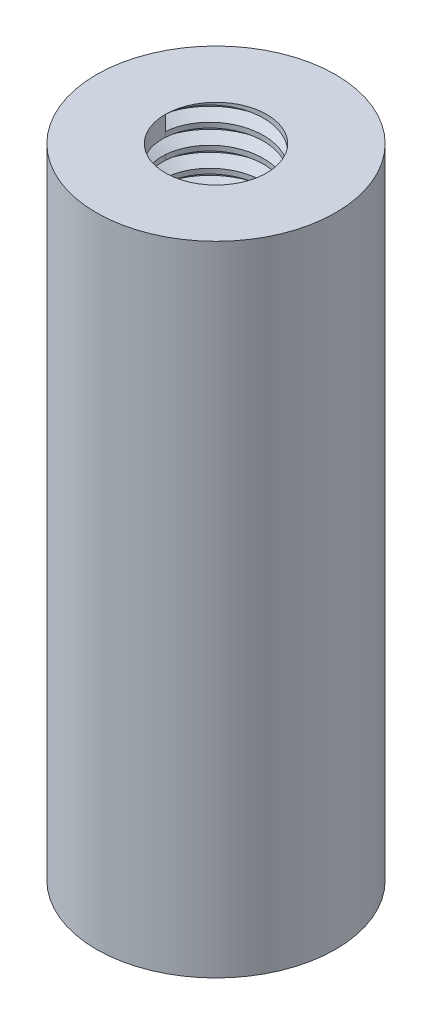
SolidWorks part; units mm, degrees
material "6061-T6 (SS)"
ref_plane "Front Plane" through (0, 0, 0) normal (0, 0, 1) x (1, 0, 0)
ref_plane "Top Plane" through (0, 0, 0) normal (0, 1, 0) x (1, 0, 0)
ref_plane "Right Plane" through (0, 0, 0) normal (1, 0, 0) x (0, 0, -1)
other "Bounding Box"
ref_plane "Default Plane" through (13.8565, 3.175, 6.7999) normal (0, -1, 0) x (-1, 0, 0)
sketch "Sketch1" plane through (0, 0, 0) normal (0, 1, 0) x (1, 0, 0)
  circle A0 centre (0, 0) radius 4.7625
  circle A1 centre (0, 0) radius 2.0193
  dimension "D1" = 9.525
  dimension "D2" = 4.0386
extrude "Boss-Extrude1" add sketch "Sketch1" along normal mid plane 25.4
thread "Thread1" pitch 0.7937 method cut profile "Thread Profile2" start angle 0, offset 0, length 9.525, pitch 0.7937, diameter 4.0386
ref_plane "Plane2" through (-2.0193, 12.7, 0) normal (0, 0, 1) x (-1, 0, 0)
sketch "Thread Profile2" plane through (-2.0193, 12.7, 0) normal (0, 0, 1) x (-1, 0, 0)
  line L0 (0, 0) -> (0, 0.7937) construction
  line L1 (0, 0) -> (0.4296, 0.248)
  line L2 (0.4296, 0.248) -> (0.4296, 0.3473)
  line L3 (0.4296, 0.3473) -> (0, 0.5953)
  line L4 (0.4296, 0.2977) -> (0, 0.2977) construction
  line L11 (0, 0) -> (0, 0.5953)
  point P2 (0, 0)
  dimension "Pitch" = 0.7937
  dimension "Profile_Angle" = 60
  dimension "Profile_Land" = 0.0992
  dimension "Profile_Height" = 0.4296
mirror "Mirror3" about plane through (0, 0, 0) normal (0, 1, 0) of "Thread1"
